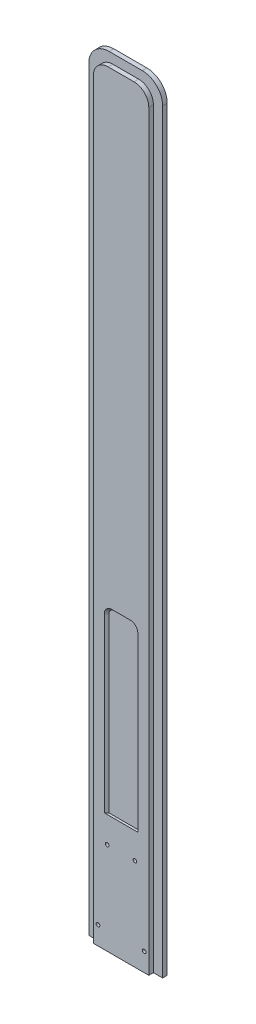
SolidWorks part; units mm, degrees
material "Acrylic (Medium-high impact)"
ref_plane "Front" through (0, 0, 0) normal (0, 0, 1) x (1, 0, 0)
ref_plane "Top" through (0, 0, 0) normal (0, 1, 0) x (1, 0, 0)
ref_plane "Right" through (0, 0, 0) normal (1, 0, 0) x (0, 0, -1)
ref_plane "new front for the battle" through (0, 0, 250.461) normal (0, 0, 1) x (1, 0, 0)
sketch "Sketch1" plane through (0, 0, 250.461) normal (0, 0, 1) x (1, 0, 0)
  line L0 (-76.9, -219) -> (-26.1, -219) construction
  line L1 (-62.9, 238.2) -> (-40.1, 238.2)
  line L2 (-76.9, 224.2) -> (-76.9, -219)
  line L4 (-26.1, 224.2) -> (-26.1, -219)
  line L5 (-76.9, 238.2) -> (-26.1, -219) construction
  line L6 (-76.9, -219) -> (-26.1, 238.2) construction
  line L8 (-76.9, -219) -> (-76.9, -295.2)
  line L9 (-76.9, -295.2) -> (-26.1, -295.2)
  line L10 (-26.1, -219) -> (-26.1, -295.2)
  arc A0 (-40.1, 238.2) -> (-26.1, 224.2) centre (-40.1, 224.2) cw
  arc A1 (-62.9, 238.2) -> (-76.9, 224.2) centre (-62.9, 224.2) ccw
  point P0 (-51.5, 9.6)
  dimension "D5" = 14
  dimension "D1" = 76.2
  dimension "D2" = 457.2
  dimension "D3" = 50.8
  dimension "D4" = 51.5
  dimension "D6" = 219
extrude "Boss-Extrude2" add sketch "Sketch1" along normal mid plane 3.175 separate body
sketch "Sketch2" plane through (0, 0, 250.461) normal (0, 0, 1) x (1, 0, 0)
  line L0 (-40.1, 238.2) -> (-62.9, 238.2) construction
  line L1 (-60.39, 231.85) -> (-42.61, 231.85)
  line L2 (-70.55, 221.69) -> (-70.55, -219)
  line L3 (-70.55, -219) -> (-32.45, -219)
  line L4 (-32.45, 221.69) -> (-32.45, -219)
  line L5 (-76.9, -219) -> (-26.1, -219) construction
  line L6 (-76.9, -295.2) -> (-26.1, -295.2) construction
  line L7 (-76.9, -295.2) -> (-26.1, -295.2) construction
  line L8 (-70.55, -219) -> (-32.45, -219)
  line L9 (-70.55, -219) -> (-70.55, -295.2)
  line L10 (-70.55, -295.2) -> (-32.45, -295.2)
  line L11 (-32.45, -219) -> (-32.45, -295.2)
  arc A0 (-42.61, 231.85) -> (-32.45, 221.69) centre (-42.61, 221.69) cw
  arc A1 (-60.39, 231.85) -> (-70.55, 221.69) centre (-60.39, 221.69) ccw
  point P4 (-51.5, 231.85)
  point P5 (-51.5, 238.2)
  point P13 (-32.45, 231.85)
  point P16 (-70.55, 231.85)
  dimension "D3" = 10.16
  dimension "D1" = 6.35
  dimension "D2" = 38.1
  dimension "D4" = 76.2
extrude "Boss-Extrude3" add sketch "Sketch2" along normal mid plane 9.525 contours L11 L3 L9 L10 | L1 A1 L2 L3 L4 A0 region at (-51.5, 5.8479, 250.461) region at (-51.5, -257.1, 250.461)
sketch "Sketch3" plane through (0, 0, 255.2235) normal (0, 0, 1) x (1, 0, 0)
  line L0 (-76.9, -219) -> (-26.1, -219) construction
  line L1 (-61.025, -219) -> (-41.975, -219)
  line L2 (-61.025, -219) -> (-61.025, -95.175)
  line L3 (-57.85, -92) -> (-45.15, -92)
  line L4 (-41.975, -219) -> (-41.975, -95.175)
  line L5 (-61.025, -213.725) -> (-41.975, -213.725)
  arc A0 (-45.15, -92) -> (-41.975, -95.175) centre (-45.15, -95.175) cw
  arc A1 (-61.025, -95.175) -> (-57.85, -92) centre (-57.85, -95.175) cw
  point P6 (-51.5, -219)
  point P10 (-41.975, -92)
  point P13 (-61.025, -92)
  dimension "D3" = 3.175
  dimension "D1" = 127
  dimension "D2" = 19.05
  dimension "D4" = 5.275
extrude "Cut-Extrude1" cut sketch "Sketch3" against normal blind 1.5875 contours A1 L2 L5 L4 A0 L3 region at (-51.5, -152.9749, 255.2235)
mirror "Mirror2" about plane through (0, 0, 250.461) normal (0, 0, 1) of "Cut-Extrude1"
chamfer "Chamfer1" distance 2 angle 45 10 edges at (-41.975, -154.45, 255.2235) (-61.025, -154.45, 255.2235) (-42.9049, -92.9299, 255.2235) (-60.0951, -92.9299, 255.2235) (-51.5, -92, 255.2235) (-41.975, -154.45, 245.6985) (-61.025, -154.45, 245.6985) (-42.9049, -92.9299, 245.6985) (-60.0951, -92.9299, 245.6985) (-51.5, -92, 245.6985)
sketch "Sketch4" plane through (0, 0, 252.0485) normal (0, 0, 1) x (1, 0, 0)
  line L0 (-76.9, -231.7) -> (-26.1, -231.7) construction
  line L1 (-76.9, 224.2) -> (-76.9, -295.2) construction
  line L2 (-26.1, -295.2) -> (-26.1, 224.2) construction
  line L3 (-61.025, -231.7) -> (-67.375, -282.5) construction
  line L4 (-67.375, -282.5) -> (-35.625, -282.5) construction
  line L5 (-35.625, -282.5) -> (-41.975, -231.7) construction
  line L6 (-76.9, -219) -> (-26.1, -219) construction
  line L8 (-76.9, -295.2) -> (-70.55, -295.2) construction
  circle A0 centre (-61.025, -231.7) radius 1.25
  circle A1 centre (-41.975, -231.7) radius 1.25
  circle A2 centre (-35.625, -282.5) radius 1.25
  circle A3 centre (-67.375, -282.5) radius 1.25
  point P10 (-51.5, -282.5)
  point P14 (-51.5, -231.7)
  dimension "D1" = 2.5
  dimension "D2" = 19.05
  dimension "D3" = 31.75
  dimension "D4" = 12.7
  dimension "D5" = 12.7
  dimension "D6" = 50.8
extrude "Cut-Extrude2" cut sketch "Sketch4" against normal through all and the other way through all
